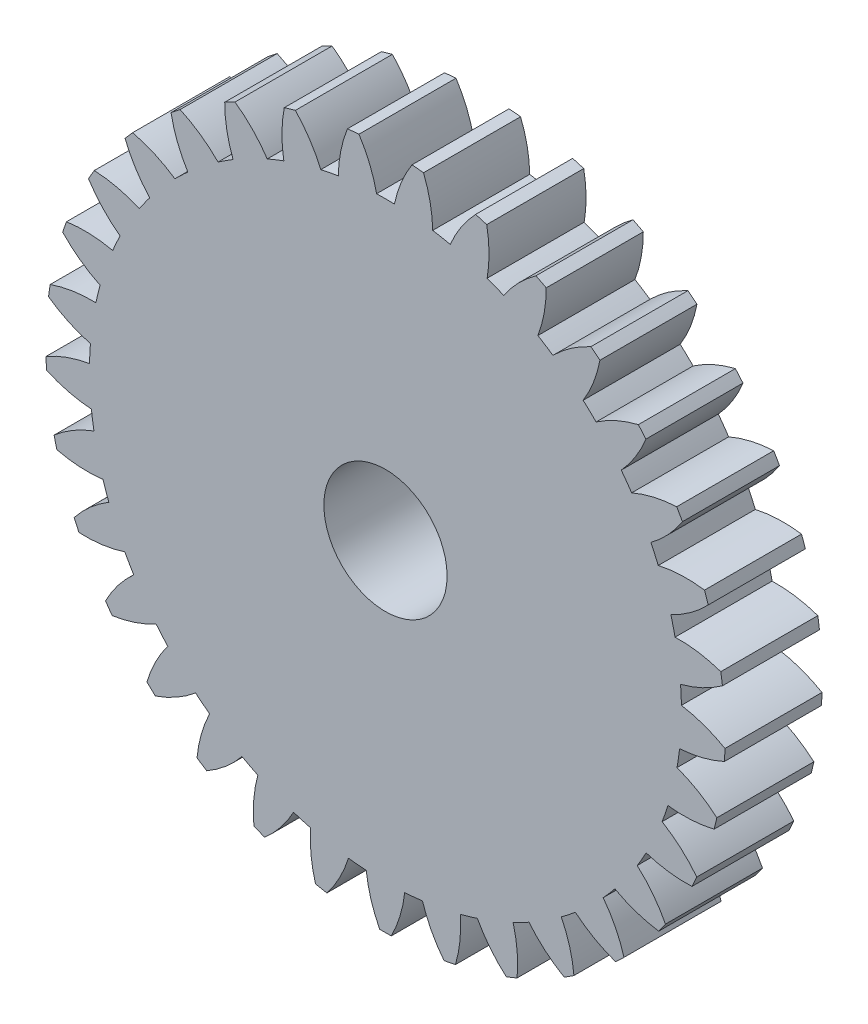
SolidWorks part; units mm, degrees
ref_plane "Alzado" through (0, 0, 0) normal (0, 0, 1) x (1, 0, 0)
ref_plane "Planta" through (0, 0, 0) normal (0, 1, 0) x (1, 0, 0)
ref_plane "Vista lateral" through (0, 0, 0) normal (1, 0, 0) x (0, 0, -1)
sketch "Croquis1" plane through (0, 0, 0) normal (0, 0, 1) x (1, 0, 0)
  line L0 (13.6206, 0) -> (-13.971, 0) construction
  line L1 (-0.46, 15.2421) -> (0, 0) construction
  line L2 (0.46, 15.2421) -> (0, 0) construction
  line L3 (1.3662, 17.4466) -> (0, 0) construction
  line L4 (1.9603, 17.3899) -> (0, 0) construction
  line L5 (0, -3.6901) -> (0, 21.5552) construction
  circle A0 centre (0, 0) radius 3.175
  arc A29 (2.4329, 15.0537) -> (1.9603, 17.3899) centre (-4.1661, 14.9347) ccw
  arc A30 (1.9603, 17.3899) -> (1.3662, 17.4466) centre (0, 0) ccw
  arc A31 (1.3662, 17.4466) -> (0.46, 15.2421) centre (6.9172, 13.8764) ccw
  arc A32 (0.46, 15.2421) -> (-0.46, 15.2421) centre (0, 0) ccw
  circle A133 centre (0, 0) radius 15.249 construction
  circle A134 centre (0, 0) radius 17.5 construction
  arc A135 (3.3363, 14.8796) -> (2.4329, 15.0537) centre (0, 0) ccw
  arc A136 (4.6433, 16.8728) -> (3.3363, 14.8796) centre (9.4183, 12.3166) ccw
  arc A137 (5.2159, 16.7046) -> (4.6433, 16.8728) centre (0, 0) ccw
  arc A138 (5.2378, 14.3212) -> (5.2159, 16.7046) centre (-1.2644, 15.4533) ccw
  arc A139 (6.092, 13.9793) -> (5.2378, 14.3212) centre (0, 0) ccw
  arc A140 (7.7526, 15.6891) -> (6.092, 13.9793) centre (11.5791, 10.3116) ccw
  arc A141 (8.283, 15.4156) -> (7.7526, 15.6891) centre (0, 0) ccw
  arc A142 (7.8535, 13.0712) -> (8.283, 15.4156) centre (1.683, 15.4133) ccw
  arc A143 (8.6275, 12.5737) -> (7.8535, 13.0712) centre (0, 0) ccw
  arc A144 (10.5816, 13.9384) -> (8.6275, 12.5737) centre (13.3213, 7.9339) ccw
  arc A145 (11.0508, 13.5695) -> (10.5816, 13.9384) centre (0, 0) ccw
  arc A146 (10.1853, 11.3487) -> (11.0508, 13.5695) centre (4.5696, 14.8163) ccw
  arc A147 (10.8512, 10.7137) -> (10.1853, 11.3487) centre (0, 0) ccw
  arc A148 (13.0283, 11.6839) -> (10.8512, 10.7137) centre (14.582, 5.2694) ccw
  arc A149 (13.4191, 11.2329) -> (13.0283, 11.6839) centre (0, 0) ccw
  arc A150 (12.149, 9.216) -> (13.4191, 11.2329) centre (7.291, 13.6837) ccw
  arc A151 (12.6827, 8.4665) -> (12.149, 9.216) centre (0, 0) ccw
  arc A152 (15.004, 9.0072) -> (12.6827, 8.4665) centre (15.3158, 2.4145) ccw
  arc A153 (15.3024, 8.4903) -> (15.004, 9.0072) centre (0, 0) ccw
  arc A154 (13.6736, 6.7502) -> (15.3024, 8.4903) centre (9.7489, 12.0566) ccw
  arc A155 (14.0558, 5.9133) -> (13.6736, 6.7502) centre (0, 0) ccw
  arc A156 (16.4375, 6.0049) -> (14.0558, 5.9133) centre (15.4959, -0.5276) ccw
  arc A157 (16.6327, 5.4409) -> (16.4375, 6.0049) centre (0, 0) ccw
  arc A158 (14.704, 4.0405) -> (16.6327, 5.4409) centre (11.8545, 9.9937) ccw
  arc A159 (14.9209, 3.1464) -> (14.704, 4.0405) centre (0, 0) ccw
  arc A160 (17.2769, 2.7855) -> (14.9209, 3.1464) centre (15.1161, -3.4507) ccw
  arc A161 (17.3618, 2.1948) -> (17.2769, 2.7855) centre (0, 0) ccw
  arc A162 (15.2029, 1.1848) -> (17.3618, 2.1948) centre (13.5316, 7.5696) ccw
  arc A163 (15.2467, 0.2657) -> (15.2029, 1.1848) centre (0, 0) ccw
  arc A164 (17.4918, -0.5345) -> (15.2467, 0.2657) centre (14.1898, -6.2491) ccw
  arc A165 (17.4634, -1.1306) -> (17.4918, -0.5345) centre (0, 0) ccw
  arc A166 (15.1524, -1.7138) -> (17.4634, -1.1306) centre (14.7196, 4.872) ccw
  arc A167 (15.0214, -2.6245) -> (15.1524, -1.7138) centre (0, 0) ccw
  arc A168 (17.0746, -3.8352) -> (15.0214, -2.6245) centre (12.7508, -8.8216) ccw
  arc A169 (16.9339, -4.4152) -> (17.0746, -3.8352) centre (0, 0) ccw
  arc A170 (14.5542, -4.5505) -> (16.9339, -4.4152) centre (15.3756, 1.9982) ccw
  arc A171 (14.2533, -5.4199) -> (14.5542, -4.5505) centre (0, 0) ccw
  arc A172 (16.0402, -6.9973) -> (14.2533, -5.4199) centre (10.8508, -11.0753) ccw
  arc A173 (15.7923, -7.5401) -> (16.0402, -6.9973) centre (0, 0) ccw
  arc A174 (13.43, -7.2226) -> (15.7923, -7.5401) centre (15.4759, -0.9477) ccw
  arc A175 (12.97, -8.0194) -> (13.43, -7.2226) centre (0, 0) ccw
  arc A176 (14.4261, -9.9064) -> (12.97, -8.0194) centre (8.5587, -12.9287) ccw
  arc A177 (14.0799, -10.3926) -> (14.4261, -9.9064) centre (0, 0) ccw
  arc A178 (11.8204, -9.6338) -> (14.0799, -10.3926) centre (15.0169, -3.8594) ccw
  arc A179 (11.2179, -10.3291) -> (11.8204, -9.6338) centre (0, 0) ccw
  arc A180 (12.2906, -12.4576) -> (11.2179, -10.3291) centre (5.9573, -14.3148) ccw
  arc A181 (11.8587, -12.8694) -> (12.2906, -12.4576) centre (0, 0) ccw
  arc A182 (9.7836, -11.6967) -> (11.8587, -12.8694) centre (14.0151, -6.6317) ccw
  arc A183 (9.0604, -12.2654) -> (9.7836, -11.6967) centre (0, 0) ccw
  arc A184 (9.7109, -14.5585) -> (9.0604, -12.2654) centre (3.1405, -15.1835) ccw
  arc A185 (9.2088, -14.8811) -> (9.7109, -14.5585) centre (0, 0) ccw
  arc A186 (7.3932, -13.3369) -> (9.2088, -14.8811) centre (12.5068, -9.1642) ccw
  arc A187 (6.5754, -13.7585) -> (7.3932, -13.3369) centre (0, 0) ccw
  arc A188 (6.7802, -16.1332) -> (6.5754, -13.7585) centre (0.2103, -15.5035) ccw
  arc A189 (6.2261, -16.355) -> (6.7802, -16.1332) centre (0, 0) ccw
  arc A190 (4.7356, -14.495) -> (6.2261, -16.355) centre (10.5465, -11.3655) ccw
  arc A191 (3.8528, -14.7543) -> (4.7356, -14.495) centre (0, 0) ccw
  arc A192 (3.6044, -17.1248) -> (3.8528, -14.7543) centre (-2.7276, -15.2631) ccw
  arc A193 (3.0184, -17.2377) -> (3.6044, -17.1248) centre (0, 0) ccw
  arc A194 (1.9068, -15.1293) -> (3.0184, -17.2377) centre (8.2049, -13.1561) ccw
  arc A195 (0.9909, -15.2168) -> (1.9068, -15.1293) centre (0, 0) ccw
  arc A196 (0.2984, -17.4975) -> (0.9909, -15.2168) centre (-5.5668, -14.4711) ccw
  arc A197 (-0.2984, -17.4975) -> (0.2984, -17.4975) centre (0, 0) ccw
  arc A198 (-0.9909, -15.2168) -> (-0.2984, -17.4975) centre (5.5668, -14.4711) ccw
  arc A199 (-1.9068, -15.1293) -> (-0.9909, -15.2168) centre (0, 0) ccw
  arc A200 (-3.0184, -17.2377) -> (-1.9068, -15.1293) centre (-8.2049, -13.1561) ccw
  arc A201 (-3.6044, -17.1248) -> (-3.0184, -17.2377) centre (0, 0) ccw
  arc A202 (-3.8528, -14.7543) -> (-3.6044, -17.1248) centre (2.7276, -15.2631) ccw
  arc A203 (-4.7356, -14.495) -> (-3.8528, -14.7543) centre (0, 0) ccw
  arc A204 (-6.2261, -16.355) -> (-4.7356, -14.495) centre (-10.5465, -11.3655) ccw
  arc A205 (-6.7802, -16.1332) -> (-6.2261, -16.355) centre (0, 0) ccw
  arc A206 (-6.5754, -13.7585) -> (-6.7802, -16.1332) centre (-0.2103, -15.5035) ccw
  arc A207 (-7.3932, -13.3369) -> (-6.5754, -13.7585) centre (0, 0) ccw
  arc A208 (-9.2088, -14.8811) -> (-7.3932, -13.3369) centre (-12.5068, -9.1642) ccw
  arc A209 (-9.7109, -14.5585) -> (-9.2088, -14.8811) centre (0, 0) ccw
  arc A210 (-9.0604, -12.2654) -> (-9.7109, -14.5585) centre (-3.1405, -15.1835) ccw
  arc A211 (-9.7836, -11.6967) -> (-9.0604, -12.2654) centre (0, 0) ccw
  arc A212 (-11.8587, -12.8694) -> (-9.7836, -11.6967) centre (-14.0151, -6.6317) ccw
  arc A213 (-12.2906, -12.4576) -> (-11.8587, -12.8694) centre (0, 0) ccw
  arc A214 (-11.2179, -10.3291) -> (-12.2906, -12.4576) centre (-5.9573, -14.3148) ccw
  arc A215 (-11.8204, -9.6338) -> (-11.2179, -10.3291) centre (0, 0) ccw
  arc A216 (-14.0799, -10.3926) -> (-11.8204, -9.6338) centre (-15.0169, -3.8594) ccw
  arc A217 (-14.4261, -9.9064) -> (-14.0799, -10.3926) centre (0, 0) ccw
  arc A218 (-12.97, -8.0194) -> (-14.4261, -9.9064) centre (-8.5587, -12.9287) ccw
  arc A219 (-13.43, -7.2226) -> (-12.97, -8.0194) centre (0, 0) ccw
  arc A220 (-15.7923, -7.5401) -> (-13.43, -7.2226) centre (-15.4759, -0.9477) ccw
  arc A221 (-16.0402, -6.9973) -> (-15.7923, -7.5401) centre (0, 0) ccw
  arc A222 (-14.2533, -5.4199) -> (-16.0402, -6.9973) centre (-10.8508, -11.0753) ccw
  arc A223 (-14.5542, -4.5505) -> (-14.2533, -5.4199) centre (0, 0) ccw
  arc A224 (-16.9339, -4.4152) -> (-14.5542, -4.5505) centre (-15.3756, 1.9982) ccw
  arc A225 (-17.0746, -3.8352) -> (-16.9339, -4.4152) centre (0, 0) ccw
  arc A226 (-15.0214, -2.6245) -> (-17.0746, -3.8352) centre (-12.7508, -8.8216) ccw
  arc A227 (-15.1524, -1.7138) -> (-15.0214, -2.6245) centre (0, 0) ccw
  arc A228 (-17.4634, -1.1306) -> (-15.1524, -1.7138) centre (-14.7196, 4.872) ccw
  arc A229 (-17.4918, -0.5345) -> (-17.4634, -1.1306) centre (0, 0) ccw
  arc A230 (-15.2467, 0.2657) -> (-17.4918, -0.5345) centre (-14.1898, -6.2491) ccw
  arc A231 (-15.2029, 1.1848) -> (-15.2467, 0.2657) centre (0, 0) ccw
  arc A232 (-17.3618, 2.1948) -> (-15.2029, 1.1848) centre (-13.5316, 7.5696) ccw
  arc A233 (-17.2769, 2.7855) -> (-17.3618, 2.1948) centre (0, 0) ccw
  arc A234 (-14.9209, 3.1464) -> (-17.2769, 2.7855) centre (-15.1161, -3.4507) ccw
  arc A235 (-14.704, 4.0405) -> (-14.9209, 3.1464) centre (0, 0) ccw
  arc A236 (-16.6327, 5.4409) -> (-14.704, 4.0405) centre (-11.8545, 9.9937) ccw
  arc A237 (-16.4375, 6.0049) -> (-16.6327, 5.4409) centre (0, 0) ccw
  arc A238 (-14.0558, 5.9133) -> (-16.4375, 6.0049) centre (-15.4959, -0.5276) ccw
  arc A239 (-13.6736, 6.7502) -> (-14.0558, 5.9133) centre (0, 0) ccw
  arc A240 (-15.3024, 8.4903) -> (-13.6736, 6.7502) centre (-9.7489, 12.0566) ccw
  arc A241 (-15.004, 9.0072) -> (-15.3024, 8.4903) centre (0, 0) ccw
  arc A242 (-12.6827, 8.4665) -> (-15.004, 9.0072) centre (-15.3158, 2.4145) ccw
  arc A243 (-12.149, 9.216) -> (-12.6827, 8.4665) centre (0, 0) ccw
  arc A244 (-13.4191, 11.2329) -> (-12.149, 9.216) centre (-7.291, 13.6837) ccw
  arc A245 (-13.0283, 11.6839) -> (-13.4191, 11.2329) centre (0, 0) ccw
  arc A246 (-10.8512, 10.7137) -> (-13.0283, 11.6839) centre (-14.582, 5.2694) ccw
  arc A247 (-10.1853, 11.3487) -> (-10.8512, 10.7137) centre (0, 0) ccw
  arc A248 (-11.0508, 13.5695) -> (-10.1853, 11.3487) centre (-4.5696, 14.8163) ccw
  arc A249 (-10.5816, 13.9384) -> (-11.0508, 13.5695) centre (0, 0) ccw
  arc A250 (-8.6275, 12.5737) -> (-10.5816, 13.9384) centre (-13.3213, 7.9339) ccw
  arc A251 (-7.8535, 13.0712) -> (-8.6275, 12.5737) centre (0, 0) ccw
  arc A252 (-8.283, 15.4156) -> (-7.8535, 13.0712) centre (-1.683, 15.4133) ccw
  arc A253 (-7.7526, 15.6891) -> (-8.283, 15.4156) centre (0, 0) ccw
  arc A254 (-6.092, 13.9793) -> (-7.7526, 15.6891) centre (-11.5791, 10.3116) ccw
  arc A255 (-5.2378, 14.3212) -> (-6.092, 13.9793) centre (0, 0) ccw
  arc A256 (-5.2159, 16.7046) -> (-5.2378, 14.3212) centre (1.2644, 15.4533) ccw
  arc A257 (-4.6433, 16.8728) -> (-5.2159, 16.7046) centre (0, 0) ccw
  arc A258 (-3.3363, 14.8796) -> (-4.6433, 16.8728) centre (-9.4183, 12.3166) ccw
  arc A259 (-2.4329, 15.0537) -> (-3.3363, 14.8796) centre (0, 0) ccw
  arc A260 (-1.9603, 17.3899) -> (-2.4329, 15.0537) centre (4.1661, 14.9347) ccw
  arc A261 (-1.3662, 17.4466) -> (-1.9603, 17.3899) centre (0, 0) ccw
  arc A262 (-0.46, 15.2421) -> (-1.3662, 17.4466) centre (-6.9172, 13.8764) ccw
  point P13 (-30.6146, 14.8176)
  point P244 (0, 0)
  dimension "D1" = 6.35
  dimension "D2" = 88.271
  dimension "D3" = 35
  dimension "D8" = 6.9172
  dimension "D11" = 30.498
  dimension "D4" = 91.729
  dimension "D5" = 94.477
  dimension "D6" = 96.432
  dimension "D7" = 13.8764
  dimension "D9" = 4.1661
  dimension "D10" = 14.9347
  dimension "D12" = 33
extrude "Saliente-Extruir1" add sketch "Croquis1" along normal blind 5
